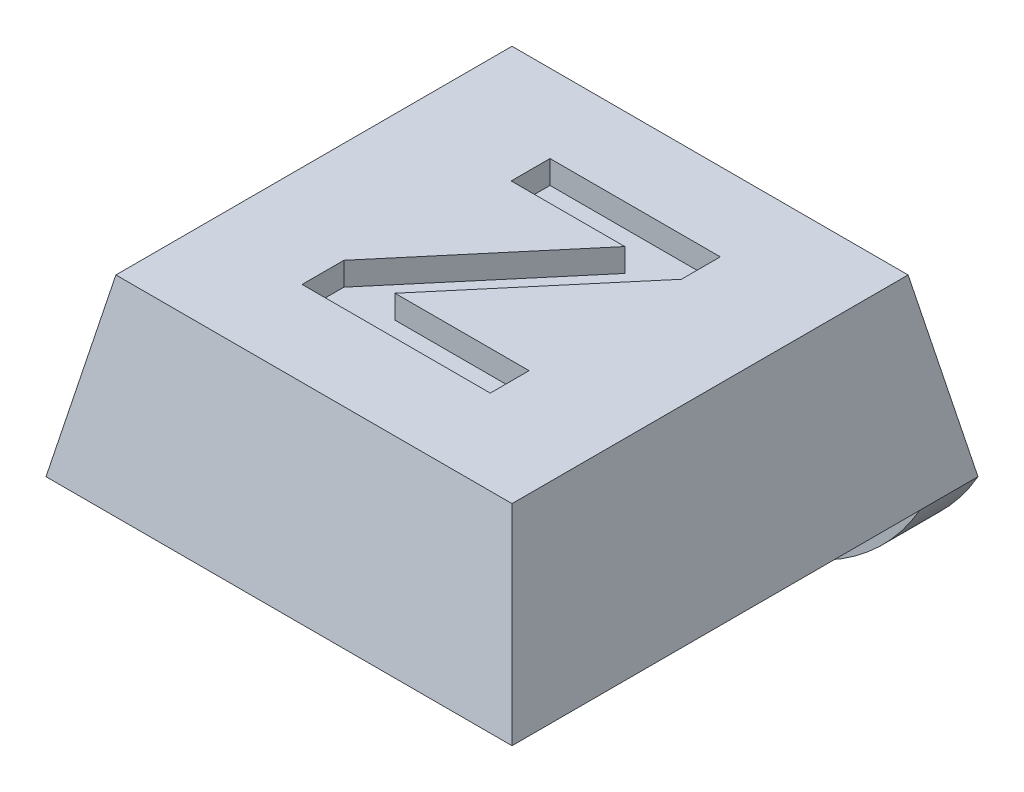
SolidWorks part; units mm, degrees
ref_plane "Front Plane" through (0, 0, 0) normal (0, 0, 1) x (1, 0, 0)
ref_plane "Top Plane" through (0, 0, 0) normal (0, 1, 0) x (1, 0, 0)
ref_plane "Right Plane" through (0, 0, 0) normal (1, 0, 0) x (0, 0, -1)
sketch "Sketch1" plane through (0, 0, 0) normal (0, 1, 0) x (1, 0, 0)
  line L1 (0, 0) -> (8, 0)
  line L2 (0, 0) -> (0, 8)
  line L3 (0, 8) -> (8, 8)
  line L4 (8, 0) -> (8, 8)
  dimension "D1" = 8
  dimension "D2" = 8
extrude "Boss-Extrude1" add sketch "Sketch1" along normal blind 3
sketch "Sketch2" plane through (0, 0, 0) normal (0, 0, 1) x (1, 0, 0)
  line L0 (0, 0) -> (0.6, 3)
  line L1 (0, 3) -> (8, 3) construction
  line L2 (0.6, 3) -> (0, 3)
  line L3 (0, 3) -> (0, 0)
  line L4 (8, 0) -> (7.4, 3)
  line L5 (7.4, 3) -> (8, 3)
  line L6 (8, 3) -> (8, 0)
  dimension "D1" = 0.6
  dimension "D2" = 0.6
extrude "Cut-Extrude1" cut sketch "Sketch2" against normal through all both and the other way through all
sketch "Sketch3" plane through (0, 0, 0) normal (1, 0, 0) x (0, 0, -1)
  line L0 (0, 0) -> (0.6, 3)
  line L1 (8, 3) -> (0, 3) construction
  line L2 (0.6, 3) -> (0, 3)
  line L3 (0, 3) -> (0, 0)
  line L4 (8, 3) -> (7.4, 3)
  line L5 (7.4, 3) -> (8, 0)
  line L6 (8, 3) -> (8, 0)
  dimension "D1" = 0.6
  dimension "D2" = 0.6
extrude "Cut-Extrude2" cut sketch "Sketch3" along normal blind 11
sketch "Sketch4" plane through (0, 0, 0) normal (0, -1, 0) x (1, 0, 0)
  line L0 (8, 0) -> (8, -8) construction
  line L3 (0, 0) -> (8, 0) construction
  circle A0 centre (4, -3.75) radius 1.8
  dimension "D1" = 3.6
  dimension "D2" = 4
  dimension "D3" = 3.75
extrude "Cut-Extrude3" cut sketch "Sketch4" against normal blind 0.8
sketch "Sketch5" plane through (0, 0, 0) normal (0, -1, 0) x (1, 0, 0)
  line L0 (8, 0) -> (8, -8) construction
  line L1 (0, -8) -> (8, -8)
  line L2 (0, -8) -> (0, -7)
  line L3 (0, -7) -> (8, -7)
  line L4 (8, -8) -> (8, -7)
  dimension "D1" = 1
extrude "Boss-Extrude2" add sketch "Sketch5" along normal blind 2
fillet "Fillet1" radius 4 2 edges at (8, -2, -7.5) (0, -2, -7.5)
sketch "Sketch6" plane through (0, 3, 0) normal (0, 1, 0) x (1, 0, 0)
  text T0 "Z" font "Arial" height 4
extrude "Cut-Extrude4" cut sketch "Sketch6" against normal blind 0.4
